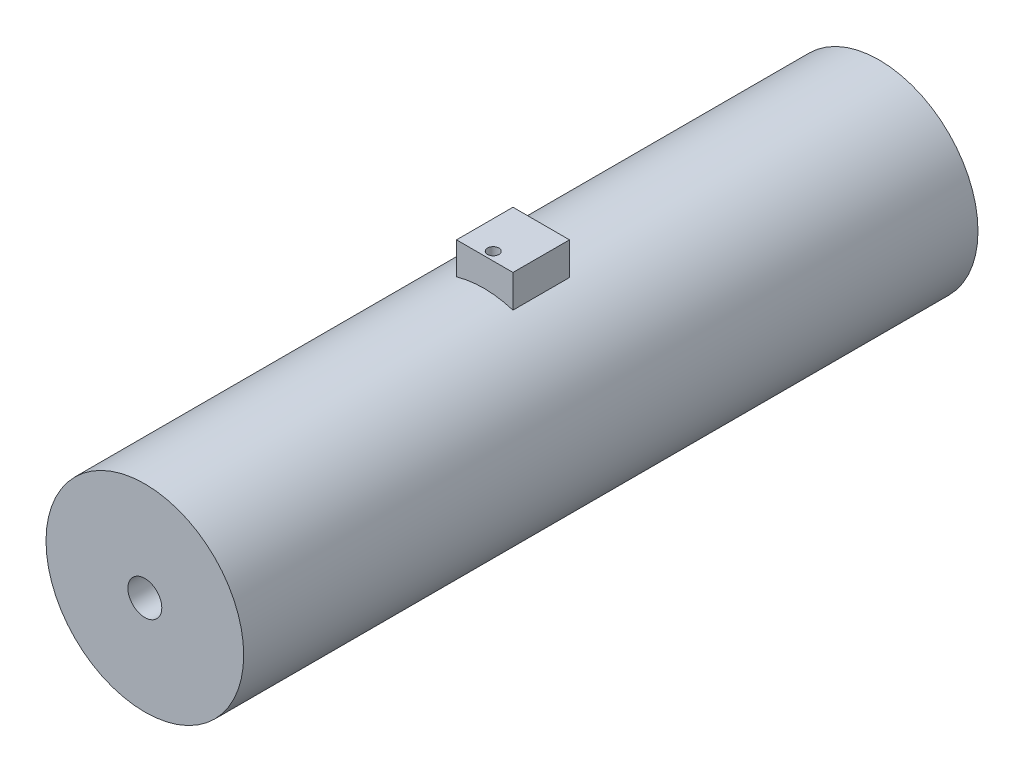
SolidWorks part; units mm, degrees
ref_plane "Front Plane" through (0, 0, 0) normal (0, 0, 1) x (1, 0, 0)
ref_plane "Top Plane" through (0, 0, 0) normal (0, 1, 0) x (1, 0, 0)
ref_plane "Right Plane" through (0, 0, 0) normal (1, 0, 0) x (0, 0, -1)
sketch "Sketch1" plane through (0, 0, 0) normal (0, 0, 1) x (1, 0, 0)
  circle A0 centre (0, 0) radius 17.5
  dimension "D1" = 35
extrude "Boss-Extrude2" add sketch "Sketch1" along normal blind 65 and the other way blind 65
ref_plane "Plane1" through (0, 0, 0) normal (0, 0, 1) x (1, 0, 0)
sketch "Sketch2" plane through (0, 0, 0) normal (0, 0, 1) x (1, 0, 0)
  line L0 (0, 0) -> (0, 12.4991)
  line L1 (-4.8243, 17.4991) -> (5.1757, 17.4991) construction
  line L2 (0.1757, 22.4991) -> (0.1757, 17.4991) construction
  line L4 (-4.8243, 22.4991) -> (5.1757, 22.4991)
  line L5 (-4.8243, 22.4991) -> (-4.8243, 12.4991)
  line L6 (-4.8243, 12.4991) -> (5.1757, 12.4991)
  line L7 (5.1757, 22.4991) -> (5.1757, 12.4991)
  circle A0 centre (0, 0) radius 17.5 construction
  dimension "D3" = 10
  dimension "D4" = 10
extrude "Boss-Extrude3" add sketch "Sketch2" along normal blind 5 and the other way blind 5 contours L7 L4 L5 L6 region at (0.1757, 17.4991, 0)
sketch "Sketch3" plane through (0, 0, 65) normal (0, 0, 1) x (1, 0, 0)
  circle A0 centre (0, 0) radius 3
  dimension "D1" = 6
extrude "Cut-Extrude1" cut sketch "Sketch3" against normal blind 15
mirror "Mirror1" about plane through (0, 0, 0) normal (0, 0, 1) of "Cut-Extrude1"
sketch "Sketch4" plane through (0, 22.4991, 0) normal (0, 1, 0) x (1, 0, 0)
  line L0 (0.1757, -5) -> (0.1757, -3.5) construction
  line L1 (-4.8243, -5) -> (5.1757, -5) construction
  circle A0 centre (0.1757, -3.5) radius 1
  dimension "D1" = 2
  dimension "D2" = 1.5
extrude "Cut-Extrude2" cut sketch "Sketch4" against normal blind 10
